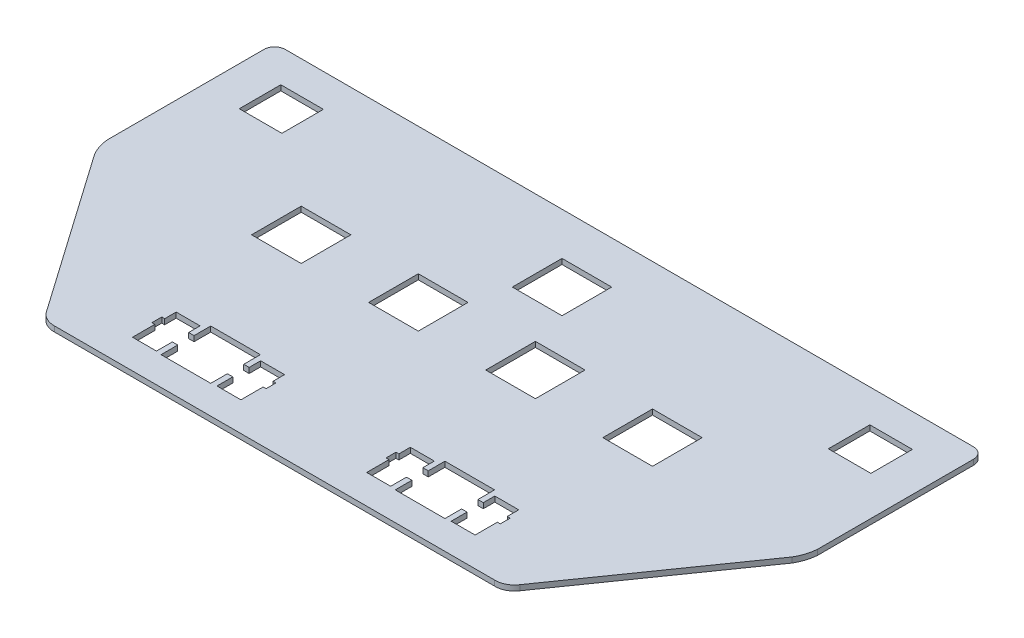
SolidWorks part; units mm, degrees
ref_plane "前视基准面" through (0, 0, 0) normal (0, 0, 1) x (1, 0, 0)
ref_plane "上视基准面" through (0, 0, 0) normal (0, 1, 0) x (1, 0, 0)
ref_plane "右视基准面" through (0, 0, 0) normal (1, 0, 0) x (0, 0, -1)
other "Configuration Table"
sketch "草图1" plane through (0, 0, 0) normal (0, 1, 0) x (1, 0, 0)
  line L0 (0, 0) -> (200, 0) construction
  line L1 (200, 0) -> (200, -100) construction
  line L2 (200, -100) -> (0, -100) construction
  line L3 (0, -100) -> (0, 0) construction
  line L4 (0, -100) -> (35, -100) construction
  line L5 (200, -100) -> (165, -100) construction
  line L6 (0, -50) -> (35, -100) construction
  line L7 (165, -100) -> (200, -50) construction
  line L8 (200, -50) -> (200, -47) construction
  line L9 (0, -50) -> (0, -47) construction
  line L10 (35, -100) -> (38, -100) construction
  line L11 (165, -100) -> (162, -100) construction
  line L12 (0, 0) -> (0, -3) construction
  line L13 (0, -3) -> (3, -3) construction
  line L14 (200, 0) -> (200, -3) construction
  line L15 (200, -3) -> (197, -3) construction
  line L16 (197, 0) -> (3, 0)
  line L17 (0, -3) -> (0, -47)
  line L18 (1.7204, -52.4577) -> (33.2796, -97.5423)
  line L19 (38, -100) -> (162, -100)
  line L20 (166.7204, -97.5423) -> (198.2796, -52.4577)
  line L21 (200, -47) -> (200, -3)
  line L22 (0, 0) -> (0, -5) construction
  line L23 (0, -5) -> (5, -5) construction
  line L24 (200, 0) -> (200, -5) construction
  line L25 (200, -5) -> (195, -5) construction
  line L26 (100, 0) -> (100, -12) construction
  line L35 (107, -12) -> (93, -12) construction
  line L36 (93, -26) -> (90.5, -26) construction
  line L37 (93, -12) -> (107, -12)
  line L38 (93, -12) -> (93, -26)
  line L39 (93, -26) -> (107, -26)
  line L40 (107, -12) -> (107, -26)
  line L41 (90.5, -26) -> (90.5, -36) construction
  line L42 (107, -26) -> (109.5, -26) construction
  line L43 (109.5, -26) -> (109.5, -36) construction
  line L44 (76.5, -36) -> (57.5, -36) construction
  line L45 (90.5, -36) -> (76.5, -36)
  line L46 (90.5, -36) -> (90.5, -50)
  line L47 (90.5, -50) -> (76.5, -50)
  line L48 (76.5, -36) -> (76.5, -50)
  line L49 (109.5, -36) -> (123.5, -36)
  line L50 (109.5, -36) -> (109.5, -50)
  line L51 (109.5, -50) -> (123.5, -50)
  line L52 (123.5, -36) -> (123.5, -50)
  line L53 (123.5, -36) -> (142.5, -36) construction
  line L54 (57.5, -36) -> (43.5, -36)
  line L55 (57.5, -36) -> (57.5, -50)
  line L56 (57.5, -50) -> (43.5, -50)
  line L57 (43.5, -36) -> (43.5, -50)
  line L58 (67, -36) -> (67, -78) construction
  line L59 (142.5, -36) -> (156.5, -36)
  line L60 (142.5, -36) -> (142.5, -50)
  line L61 (142.5, -50) -> (156.5, -50)
  line L62 (156.5, -36) -> (156.5, -50)
  line L63 (133, -36) -> (133, -78) construction
  line L64 (60, -78) -> (74, -78) construction
  line L65 (140, -78) -> (126, -78) construction
  line L66 (5, -5) -> (5, -15.1) construction
  line L67 (60, -78) -> (74, -78)
  line L69 (60, -92) -> (74, -92)
  line L71 (140, -78) -> (126, -78)
  line L73 (140, -92) -> (126, -92)
  line L75 (5, -15.1) -> (11, -15.1) construction
  line L76 (195, -5) -> (195, -15.1) construction
  line L77 (11, -20.95) -> (23, -20.95)
  line L78 (11, -20.95) -> (11, -9.25)
  line L79 (11, -9.25) -> (23, -9.25)
  line L80 (23, -20.95) -> (23, -9.25)
  line L81 (195, -15.1) -> (189, -15.1) construction
  line L82 (74, -78) -> (74, -82.7)
  line L83 (189, -20.95) -> (177, -20.95)
  line L84 (189, -20.95) -> (189, -9.25)
  line L85 (189, -9.25) -> (177, -9.25)
  line L86 (177, -20.95) -> (177, -9.25)
  line L87 (74, -92) -> (74, -87.3)
  line L88 (74, -82.7) -> (75.525, -82.7)
  line L89 (74, -87.3) -> (75.525, -87.3)
  line L90 (75.525, -82.7) -> (75.525, -79.47)
  line L91 (75.525, -87.3) -> (75.525, -91.77)
  line L92 (75.525, -79.47) -> (82.275, -79.47)
  line L93 (82.275, -79.47) -> (82.275, -82.7)
  line L94 (82.275, -82.7) -> (83.1, -82.7)
  line L95 (83.1, -82.7) -> (83.1, -85.5)
  line L96 (83.1, -85.5) -> (82.275, -85.5)
  line L97 (82.275, -85.5) -> (82.275, -91.77)
  line L98 (82.275, -91.77) -> (75.525, -91.77)
  line L101 (60, -78) -> (60, -82.7)
  line L102 (60, -92) -> (60, -87.3)
  line L103 (60, -82.7) -> (58.475, -82.7)
  line L104 (58.475, -82.7) -> (58.475, -79.47)
  line L105 (58.475, -79.47) -> (51.725, -79.47)
  line L106 (51.725, -79.47) -> (51.725, -82.7)
  line L107 (51.725, -82.7) -> (50.9, -82.7)
  line L108 (50.9, -82.7) -> (50.9, -85.5)
  line L109 (50.9, -85.5) -> (51.725, -85.5)
  line L110 (51.725, -85.5) -> (51.725, -91.77)
  line L111 (51.725, -91.77) -> (58.475, -91.77)
  line L112 (58.475, -91.77) -> (58.475, -87.3)
  line L113 (58.475, -87.3) -> (60, -87.3)
  line L114 (140, -78) -> (140, -82.7)
  line L115 (140, -82.7) -> (141.525, -82.7)
  line L116 (141.525, -82.7) -> (141.525, -79.47)
  line L117 (141.525, -79.47) -> (148.275, -79.47)
  line L118 (148.275, -79.47) -> (148.275, -82.7)
  line L119 (148.275, -82.7) -> (149.1, -82.7)
  line L120 (149.1, -82.7) -> (149.1, -85.5)
  line L121 (149.1, -85.5) -> (148.275, -85.5)
  line L122 (148.275, -85.5) -> (148.275, -91.77)
  line L123 (148.275, -91.77) -> (141.525, -91.77)
  line L124 (141.525, -91.77) -> (141.525, -87.3)
  line L125 (141.525, -87.3) -> (140, -87.3)
  line L126 (140, -87.3) -> (140, -92)
  line L127 (126, -78) -> (126, -82.7)
  line L128 (126, -82.7) -> (124.475, -82.7)
  line L129 (124.475, -82.7) -> (124.475, -79.47)
  line L130 (124.475, -79.47) -> (117.725, -79.47)
  line L131 (117.725, -79.47) -> (117.725, -82.7)
  line L132 (117.725, -82.7) -> (116.9, -82.7)
  line L133 (116.9, -82.7) -> (116.9, -85.5)
  line L134 (116.9, -85.5) -> (117.725, -85.5)
  line L135 (117.725, -85.5) -> (117.725, -91.77)
  line L136 (117.725, -91.77) -> (124.475, -91.77)
  line L137 (124.475, -91.77) -> (124.475, -87.3)
  line L138 (124.475, -87.3) -> (126, -87.3)
  line L139 (126, -87.3) -> (126, -92)
  arc A0 (200, -47) -> (198.2796, -52.4577) centre (200, -50) ccw construction
  arc A1 (200, -47) -> (198.2796, -52.4577) centre (197.1388, -49.0981) ccw construction
  arc A2 (200, -47) -> (198.2796, -52.4577) centre (193.7549, -48.0314) ccw construction
  arc A3 (200, -47) -> (198.2796, -52.4577) centre (187.718, -46.1284) cw
  arc A4 (0, -47) -> (1.7204, -52.4577) centre (0, -50) cw construction
  arc A5 (0, -47) -> (1.7204, -52.4577) centre (2.8612, -49.0981) cw construction
  arc A6 (0, -47) -> (1.7204, -52.4577) centre (6.2451, -48.0314) cw construction
  arc A7 (0, -47) -> (1.7204, -52.4577) centre (12.282, -46.1284) ccw
  arc A8 (38, -100) -> (33.2796, -97.5423) centre (35, -100) ccw construction
  arc A9 (38, -100) -> (33.2796, -97.5423) centre (36.3854, -97.3391) ccw construction
  arc A10 (33.2796, -97.5423) -> (38, -100) centre (37.8228, -94.5784) ccw
  arc A11 (162, -100) -> (166.7204, -97.5423) centre (165, -100) cw construction
  arc A12 (162, -100) -> (166.7204, -97.5423) centre (163.6146, -97.3391) cw construction
  arc A13 (162, -100) -> (166.7204, -97.5423) centre (162.1772, -94.5784) ccw
  arc A14 (0, -3) -> (3, 0) centre (3, -3) cw
  arc A15 (200, -3) -> (197, 0) centre (197, -3) ccw
  point P48 (100, -12)
  point P75 (67, -78)
  point P78 (133, -78)
  point P135 (0, 0)
  point P137 (152.7825, -82.6764)
  point P138 (114.3576, -82.4704)
  dimension "D12" = 3
  dimension "D10" = 3
  dimension "D1" = 200
  dimension "D2" = 100
  dimension "D3" = 35
  dimension "D4" = 35
  dimension "D5" = 3
  dimension "D6" = 3
  dimension "D7" = 3
  dimension "D8" = 3
  dimension "D9" = 44
  dimension "D11" = 44
  dimension "D13" = 5
  dimension "D14" = 5
  dimension "D15" = 5
  dimension "D16" = 5
  dimension "D17" = 10.1
  dimension "D18" = 6
  dimension "D19" = 10.1
  dimension "D20" = 6
  dimension "D21" = 12
  dimension "D22" = 14
  dimension "D23" = 14
  dimension "D24" = 2.5
  dimension "D25" = 10
  dimension "D26" = 2.5
  dimension "D27" = 10
  dimension "D28" = 14
  dimension "D29" = 14
  dimension "D30" = 14
  dimension "D31" = 14
  dimension "D32" = 19
  dimension "D33" = 14
  dimension "D34" = 14
  dimension "D35" = 19
  dimension "D36" = 14
  dimension "D37" = 14
  dimension "D38" = 42
  dimension "D39" = 42
  dimension "D40" = 14
  dimension "D41" = 14
  dimension "D42" = 4.7
  dimension "D43" = 14
  dimension "D44" = 12
  dimension "D45" = 11.7
  dimension "D46" = 4.7
  dimension "D47" = 4.7
  dimension "D48" = 11.7
  dimension "D49" = 12
  dimension "D50" = 4.7
  dimension "D51" = 4.6
  dimension "D52" = 4.6
  dimension "D53" = 1.525
  dimension "D54" = 1.525
  dimension "D55" = 1.525
  dimension "D56" = 3.23
  dimension "D57" = 3.23
  dimension "D58" = 6.75
  dimension "D59" = 6.75
  dimension "D60" = 3.23
  dimension "D61" = 0.825
  dimension "D62" = 2.8
  dimension "D63" = 0.825
  dimension "D64" = 6.27
  dimension "D65" = 3.23
  dimension "D66" = 0.825
  dimension "D67" = 2.8
  dimension "D68" = 0.825
  dimension "D69" = 6.27
  dimension "D70" = 6.75
  dimension "D71" = 4.7
  dimension "D72" = 1.525
  dimension "D73" = 3.23
  dimension "D74" = 6.75
  dimension "D75" = 3.23
  dimension "D76" = 0.825
  dimension "D77" = 2.8
  dimension "D78" = 0.825
  dimension "D79" = 6.27
  dimension "D80" = 6.75
  dimension "D81" = 4.47
  dimension "D82" = 1.525
  dimension "D83" = 4.7
  dimension "D84" = 4.7
  dimension "D85" = 1.525
  dimension "D86" = 3.23
  dimension "D87" = 6.75
  dimension "D88" = 3.23
  dimension "D89" = 0.825
  dimension "D90" = 2.8
  dimension "D91" = 0.825
  dimension "D92" = 6.27
  dimension "D93" = 6.75
  dimension "D94" = 4.47
  dimension "D95" = 1.525
  dimension "D96" = 4.7
extrude "凸台-拉伸1" add sketch "草图1" along normal blind 1.5
